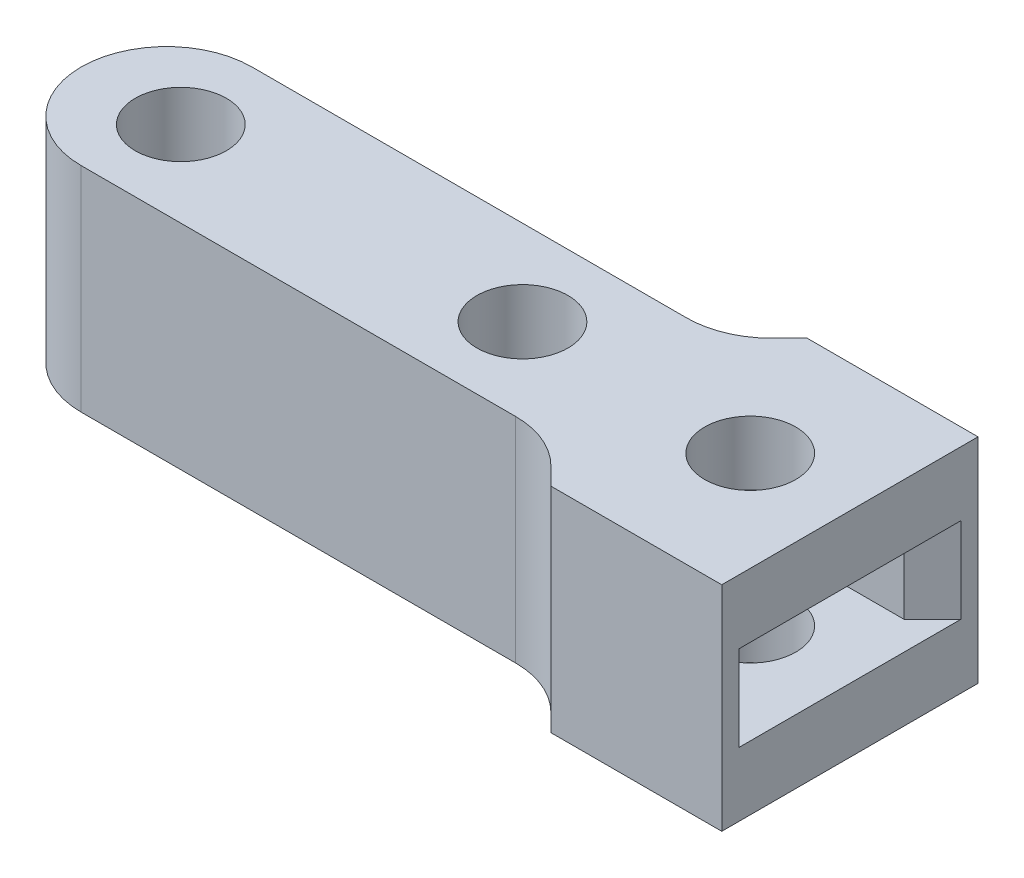
SolidWorks part; units mm, degrees
ref_plane "Front Plane" through (0, 0, 0) normal (0, 0, 1) x (1, 0, 0)
ref_plane "Top Plane" through (0, 0, 0) normal (0, 1, 0) x (1, 0, 0)
ref_plane "Right Plane" through (0, 0, 0) normal (1, 0, 0) x (0, 0, -1)
sketch "Sketch1" plane through (0, 0, 0) normal (0, 1, 0) x (1, 0, 0)
  line L0 (10, 0) -> (-10, 0) construction
  line L1 (-13.5, 3) -> (6, 3)
  line L2 (-13.5, 3) -> (-13.5, -3)
  line L3 (6, 3) -> (7.5, 4.5)
  line L4 (7.5, 4.5) -> (13.5, 4.5)
  line L5 (13.5, 4.5) -> (13.5, -4.5)
  line L6 (13.5, -4.5) -> (7.5, -4.5)
  line L7 (7.5, -4.5) -> (6, -3)
  line L8 (6, -3) -> (-13.5, -3)
  circle A0 centre (2, 0) radius 1.6
  circle A2 centre (-10, 0) radius 1.6
  circle A3 centre (10, 0) radius 1.6
  point P0 (0, 0)
  point P3 (-13.5, 0)
  point P17 (13.5, 0)
  dimension "D1" = 3.2
  dimension "D3" = 8
  dimension "D2" = 20
  dimension "D4" = 3
  dimension "D5" = 27
  dimension "D6" = 9
  dimension "D7" = 13.5
  dimension "D8" = 90
  dimension "D9" = 6
extrude "Boss-Extrude1" add sketch "Sketch1" along normal blind 7.5
ref_plane "Plane1" through (0, 3.75, 0) normal (0, 1, 0) x (1, 0, 0)
sketch "Sketch2" plane through (0, 3.75, 0) normal (0, 1, 0) x (1, 0, 0)
  line L0 (13.5, -2.9) -> (13.5, 2.9)
  line L1 (13.5, 2.9) -> (8.0213, 2.9)
  line L2 (8.0213, 2.9) -> (6.6514, 1.53)
  line L3 (6.6514, 1.53) -> (6.6514, -1.53)
  line L4 (8.0213, -2.9) -> (13.5, -2.9)
  line L5 (13.5, -4.5) -> (13.5, 4.5) construction
  line L6 (13.3486, 0) -> (11.6743, 2.9) construction
  line L7 (11.6743, 2.9) -> (8.3257, 2.9) construction
  line L8 (8.3257, 2.9) -> (6.6514, 0) construction
  line L9 (6.6514, 0) -> (8.3257, -2.9) construction
  line L10 (8.3257, -2.9) -> (11.6743, -2.9) construction
  line L11 (11.6743, -2.9) -> (13.3486, 0) construction
  line L12 (6.6514, -1.53) -> (8.0213, -2.9)
  line L13 (7.5, 4.5) -> (6, 3) construction
  line L14 (6, -3) -> (7.5, -4.5) construction
  circle A0 centre (10, 0) radius 2.9 construction
  point P2 (13.5, 0)
  dimension "D1" = 5.8
  dimension "D2" = 1.5
extrude "Cut-Extrude1" cut sketch "Sketch2" against normal mid plane 3
chamfer "Chamfer1" distance 1 angle 45 2 edges at (13.5, 3.75, 2.9) (13.5, 3.75, -2.9)
fillet "Fillet1" radius 3 4 edges at (-13.5, 3.75, -3) (-13.5, 3.75, 3) (6, 3.75, -3) (6, 3.75, 3)
